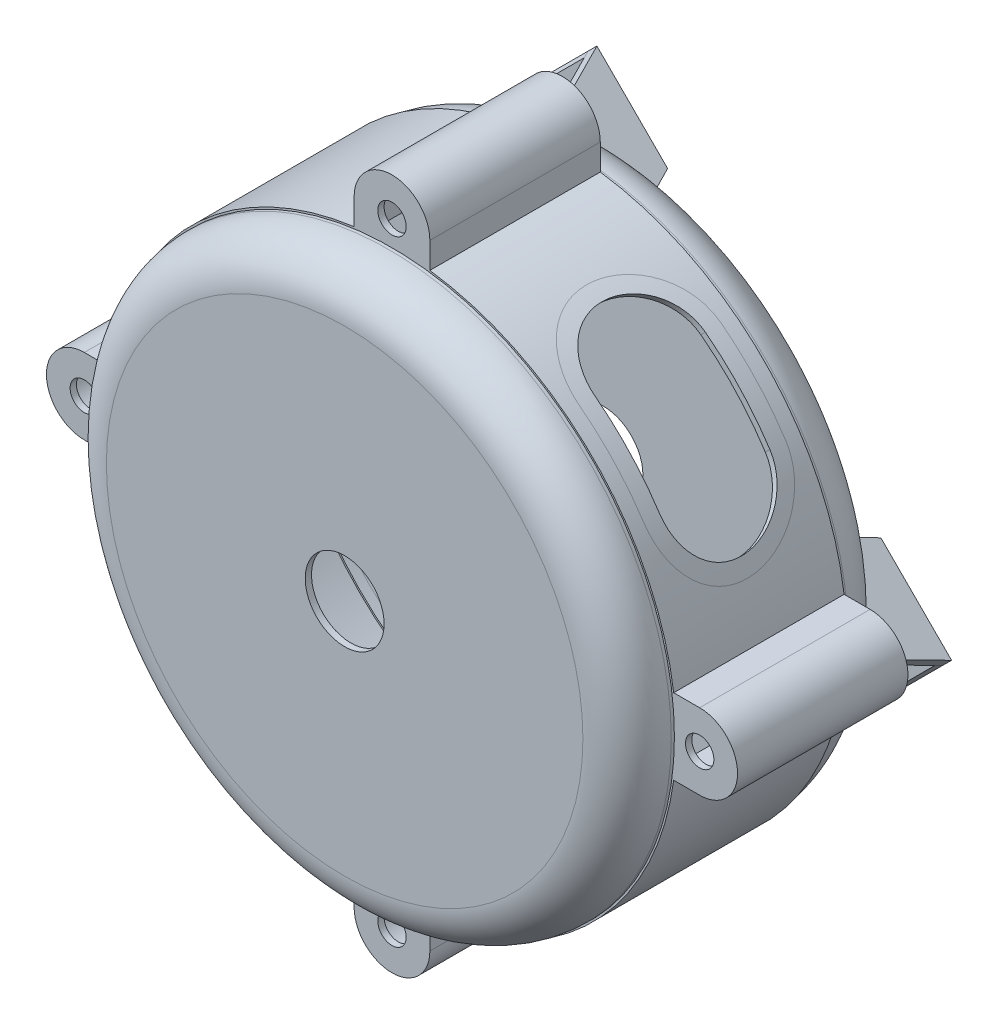
SolidWorks part; units mm, degrees
other "Markup1"
sketch "Sketch6" plane through (154, 154, 84) normal (0.5187, 0.5643, 0.6423) x (0.7927, -0.0361, -0.6085)
ref_plane "Front Plane" through (0, 0, 0) normal (0, 0, 1) x (1, 0, 0)
ref_plane "Top Plane" through (0, 0, 0) normal (0, 1, 0) x (1, 0, 0)
ref_plane "Right Plane" through (0, 0, 0) normal (1, 0, 0) x (0, 0, -1)
sketch "Sketch1" plane through (0, 0, 0) normal (0, 0, 1) x (1, 0, 0)
  line L8 (175, 20) -> (195, 20)
  line L9 (20, 175) -> (20, 195)
  line L10 (-20, 175) -> (-20, 195)
  line L11 (175, -20) -> (195, -20)
  line L12 (20, -175) -> (20, -195)
  line L13 (-20, -175) -> (-20, -195)
  line L14 (-175, -20) -> (-195, -20)
  line L15 (-175, 20) -> (-195, 20)
  arc A11 (20, 195) -> (-20, 195) centre (0, 195) ccw
  arc A14 (195, -20) -> (195, 20) centre (195, 0) ccw
  arc A15 (-20, -195) -> (20, -195) centre (0, -195) ccw
  arc A16 (-195, 20) -> (-195, -20) centre (-195, 0) ccw
  arc A17 (-175, -20) -> (-20, -175) centre (0, 0) ccw
  arc A18 (-20, 175) -> (-175, 20) centre (0, 0) ccw
  arc A19 (175, 20) -> (20, 175) centre (0, 0) ccw
  arc A20 (20, -175) -> (175, -20) centre (0, 0) ccw
  point P27 (0, 0)
  point P33 (0, 0)
  dimension "D2" = 20
  dimension "D3" = 4
extrude "Boss-Extrude1" add sketch "Sketch1" along normal blind 100
sketch "Sketch3" plane through (0, 0, 100) normal (0, 0, 1) x (1, 0, 0)
  circle A0 centre (0, 0) radius 175
  dimension "D1" = 350
extrude "Boss-Extrude2" add sketch "Sketch3" along normal blind 30
sketch "Sketch4" plane through (0, 0, 0) normal (0, 0, -1) x (-1, 0, 0)
  circle A0 centre (0, 0) radius 175
  dimension "D1" = 350
extrude "Boss-Extrude3" add sketch "Sketch4" along normal blind 30
fillet "Fillet1" radius 24 2 edges at (-175, 0, -30) (175, 0, 130)
sketch "Sketch5" plane through (0, 0, 130) normal (0, 0, 1) x (1, 0, 0)
  circle A0 centre (0, 0) radius 25
  dimension "D1" = 50
extrude "Cut-Extrude2" cut sketch "Sketch5" against normal through all
shell "Shell7" thickness 4 removed face at (25, 0, -30) outward yes
sketch "Sketch10" plane through (0, 0, 0) normal (1, 0, 0) x (0, 0, -1)
  line L0 (-142.2339, 0) -> (41.6231, 0)
ref_plane "Plane2" through (0, 0, 0) normal (0.7071, 0.7071, 0) x (0, 0, -1)
sketch "Sketch11" plane through (0, 0, 0) normal (0.7071, 0.7071, 0) x (0, 0, -1)
  line L0 (-95, 23.5966) -> (-95, -36.4034)
  line L5 (-50, 68.5966) -> (-50, -81.4034) construction
  line L6 (-5, 23.5966) -> (-5, -36.4034)
  line L7 (-15, 23.5966) -> (-15, -36.4034)
  line L8 (-85, 23.5966) -> (-85, -36.4034)
  arc A0 (-95, -36.4034) -> (-5, -36.4034) centre (-50, -36.4034) ccw
  arc A1 (-95, 23.5966) -> (-5, 23.5966) centre (-50, 23.5966) cw
  arc A2 (-85, 23.5966) -> (-15, 23.5966) centre (-50, 23.5966) cw
  arc A3 (-85, -36.4034) -> (-15, -36.4034) centre (-50, -36.4034) ccw
  point P8 (-95, 68.5966)
  dimension "D3" = 45
  dimension "D1" = 10
split line "Split Line2"
extrude "Cut-Extrude3" cut sketch "Sketch11<2>" along normal through all contours A2 L7 A3 L8
sketch "Sketch11<2>" plane through (0, 0, 0) normal (0.7071, 0.7071, 0) x (0, 0, -1) same geometry as "Sketch11"
sketch "Sketch14" plane through (0, 0, -4) normal (0, 0, -1) x (-1, 0, 0)
  circle A0 centre (0, 195) radius 9
  circle A1 centre (195, 0) radius 9
  circle A2 centre (0, -195) radius 9
  circle A3 centre (-195, 0) radius 9
  point P12 (0, 0)
  dimension "D1" = 18
  dimension "D2" = 4
extrude "Cut-Extrude4" cut sketch "Sketch14" against normal through all
sketch "Sketch16" plane through (0, 0, -34) normal (0, 0, -1) x (-1, 0, 0)
  line L0 (0, 151) -> (0, -151) construction
  line L1 (151, 0) -> (-151, 0) construction
  line L2 (57.4407, 122.6385) -> (118.9536, 61.1255)
  line L3 (118.9536, 61.1255) -> (79.6394, 21.8112)
  line L4 (79.6394, 21.8112) -> (18.1264, 83.3242)
  line L5 (18.1264, 83.3242) -> (57.4407, 122.6385)
  line L8 (0, 75.5) -> (75.5, 0) construction
  line L9 (0, 75.5) -> (-75.5, 0) construction
  circle A0 centre (0, 0) radius 151 construction
extrude "Cut-Extrude5" cut sketch "Sketch16" against normal blind 50
sketch "Sketch17" plane through (0, 0, -34) normal (0, 0, -1) x (-1, 0, 0)
  line L0 (57.4407, 122.6385) -> (51.7838, 128.2953)
  line L1 (51.7838, 128.2953) -> (6.8127, 83.3242)
  line L2 (6.8127, 83.3242) -> (79.6394, 10.4975)
  line L3 (79.6394, 10.4975) -> (124.6105, 55.4686)
  line L4 (124.6105, 55.4686) -> (118.9536, 61.1255)
  line L5 (79.6394, 21.8112) -> (118.9536, 61.1255) construction
  line L6 (118.9536, 61.1255) -> (79.6394, 21.8112)
  line L7 (79.6394, 21.8112) -> (18.1264, 83.3242)
  line L8 (18.1264, 83.3242) -> (57.4407, 122.6385)
  point P13 (48.8829, 52.5677)
  dimension "D1" = 8
  dimension "D2" = 8
  dimension "D3" = 8
ref_plane "Plane3" through (0, 0, -100) normal (0, 0, 1) x (1, 0, 0)
sketch "Sketch18" plane through (0, 0, -100) normal (0, 0, 1) x (1, 0, 0)
  line L0 (-29.2982, 105.8098) -> (-74.1288, 150.6403)
  line L1 (-51.7838, 128.2953) -> (-6.8127, 83.3242) construction
  line L2 (-74.1288, 150.6403) -> (-79.7857, 144.9835)
  line L3 (-79.7857, 144.9835) -> (-40.6119, 105.8098)
  line L4 (-18.1264, 83.3242) -> (-57.4407, 122.6385) construction
  line L5 (-40.6119, 105.8098) -> (-102.1249, 44.2968)
  line L6 (-118.9536, 61.1255) -> (-79.6394, 21.8112) construction
  line L7 (-102.1249, 44.2968) -> (-141.2986, 83.4705)
  line L8 (-141.2986, 83.4705) -> (-146.9555, 77.8136)
  line L9 (-146.9555, 77.8136) -> (-102.1249, 32.9831)
  line L10 (-79.6394, 10.4975) -> (-124.6105, 55.4686) construction
  line L11 (-102.1249, 32.9831) -> (-29.2982, 105.8098)
  dimension "D2" = 8
  dimension "D3" = 8
  dimension "D4" = 8
extrude "Boss-Extrude4" add sketch "Sketch18" along normal blind 0.01 separate body
extrude "Boss-Extrude5" add sketch "Sketch17" along normal blind 0.01 separate body
loft "Loft1" add section face at (-67.1258, 70.8106, -34.01) section face at (-89.5411, 93.2259, -99.99) connector at (-79.6394, 21.8112, -34.01) connector at (-102.1249, 44.2968, -99.99)
sketch "Sketch19" plane through (-28.9141, -28.9141, 0) normal (0.7071, 0.7071, 0) x (0, 0, -1)
  line L0 (100, 158.9358) -> (96.3906, 157.2119)
  line L1 (34.01, 127.3352) -> (99.99, 158.9358) construction
  line L2 (96.3906, 157.2119) -> (96.3906, 101.801)
  line L3 (34.01, 71.7364) -> (99.99, 103.5358) construction
  line L4 (96.3906, 101.801) -> (100, 103.5358)
  line L5 (100, 103.5358) -> (100, 158.9358)
  dimension "D1" = 4
extrude "Boss-Extrude6" add sketch "Sketch19" along normal up to vertex (86.9925 mm away) up to point (-40.6119, 105.8098, -100)
sketch "Sketch21" plane through (0, 0, 0) normal (0, 1, 0) x (1, 0, 0)
  line L0 (0, 112.5398) -> (0, -142.3862)
ref_plane "Plane4" through (0, 0, 0) normal (-0.7071, 0.7071, 0) x (0, 0, 1)
mirror "Mirror1" about plane through (0, 0, 0) normal (-0.7071, 0.7071, 0) of bodies 117
mirror "Mirror2" about plane through (0, 0, 0) normal (-0.7071, 0.7071, 0) of "Cut-Extrude5"
sketch "Sketch22" plane through (32.5989, 32.5989, 0) normal (-0.7071, -0.7071, 0) x (0, 0, 1)
  line L0 (-30, 127.3352) -> (-34, 127.3352)
  line L1 (-34, 127.3352) -> (-34, 71.7364)
  line L2 (-34, 71.7364) -> (-30, 71.7364)
  line L3 (-30, 71.7364) -> (-30, 127.3352)
extrude "Boss-Extrude7" add sketch "Sketch22" along normal up to next
